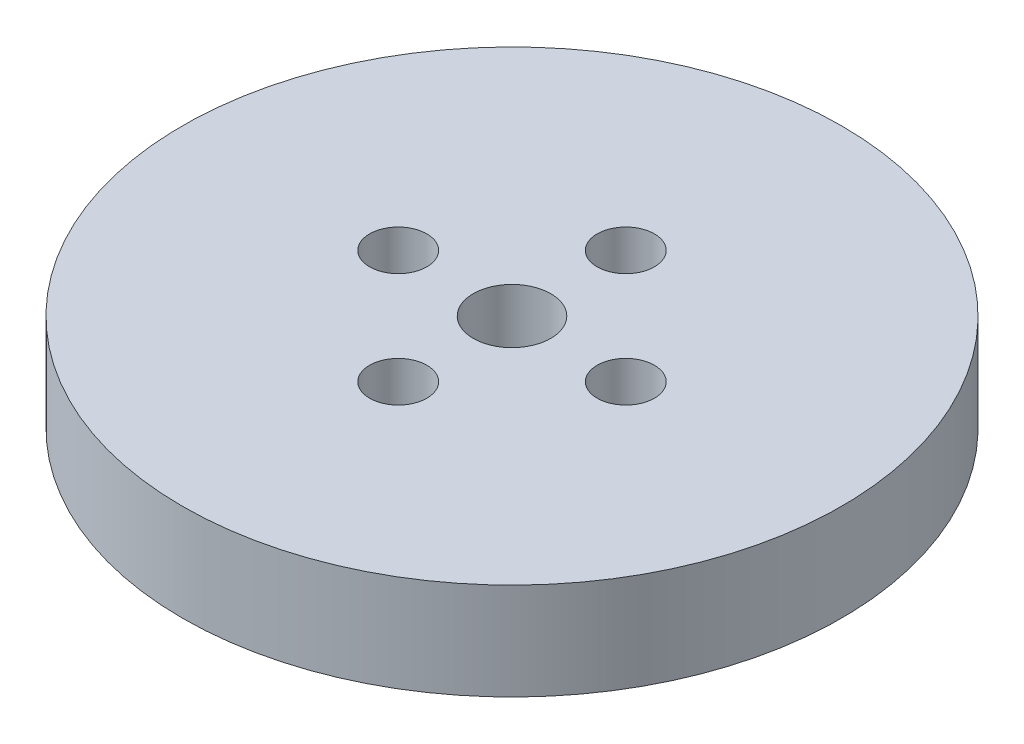
SolidWorks part; units mm, degrees
ref_plane "Front Plane" through (0, 0, 0) normal (0, 0, 1) x (1, 0, 0)
ref_plane "Top Plane" through (0, 0, 0) normal (0, 1, 0) x (1, 0, 0)
ref_plane "Right Plane" through (0, 0, 0) normal (1, 0, 0) x (0, 0, -1)
sketch "Sketch1" plane through (0, 0, 0) normal (0, 1, 0) x (1, 0, 0)
  circle A0 centre (0, 0) radius 85
  dimension "FLANGE_OD" = 170
extrude "Boss-Extrude1" add sketch "Sketch1" along normal blind 25
sketch "Sketch2" plane through (0, 0, 0) normal (0, 1, 0) x (1, 0, 0)
  circle A0 centre (0, 0) radius 10
  dimension "BORE_D" = 20
extrude "Cut-Extrude1" cut sketch "Sketch2" along normal through all
sketch "Sketch3" plane through (0, 25, 0) normal (0, 1, 0) x (1, 0, 0)
  circle A0 centre (0, 0) radius 29.3465 construction
  circle A1 centre (-29.3465, 0) radius 7.3807
  dimension "BOLT_D" = 14.7614
  dimension "BOLT_PCD" = 58.6931
extrude "Cut-Extrude2" cut sketch "Sketch3" against normal blind 22.6203
pattern_circular "CirPattern1" count 4 over 360 about axis through (0, 0, 0) along (0, 1, 0) of "Cut-Extrude2"
